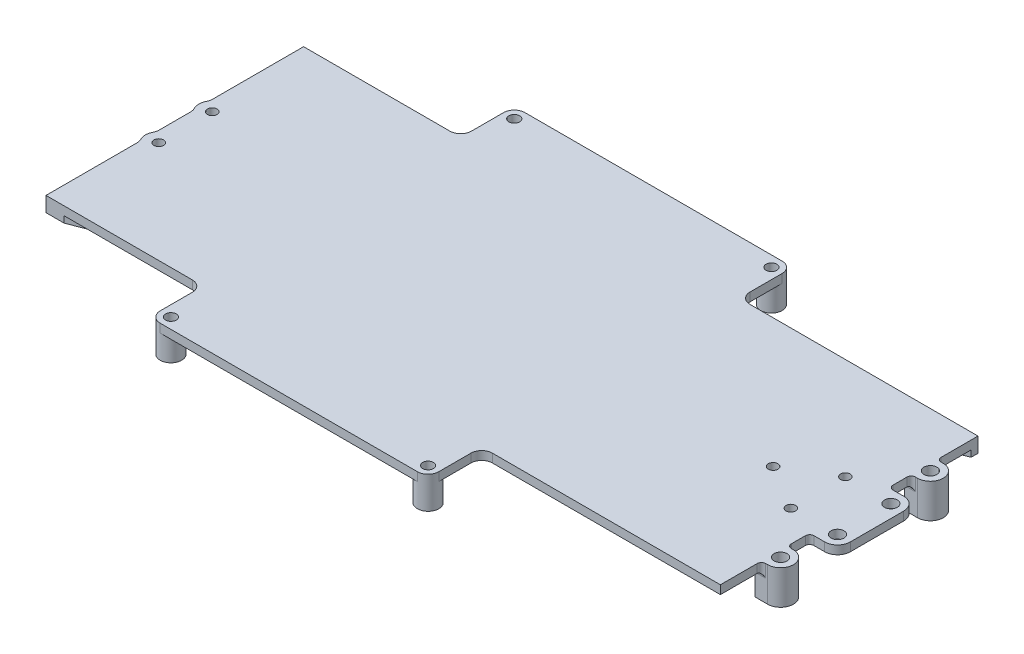
SolidWorks part; units mm, degrees
ref_plane "Front Plane" through (0, 0, 0) normal (0, 0, 1) x (1, 0, 0)
ref_plane "Top Plane" through (0, 0, 0) normal (0, 1, 0) x (1, 0, 0)
ref_plane "Right Plane" through (0, 0, 0) normal (1, 0, 0) x (0, 0, -1)
ref_point "Point1"
ref_point "Point2"
sketch "Sketch1" plane through (0, 0, 0) normal (0, 1, 0) x (1, 0, 0)
  line L0 (-51.1882, 59.7128) -> (-51.1882, -20.4872)
  line L1 (-51.1882, 59.7128) -> (-51.1882, 79.7128)
  line L2 (-51.1882, -20.4872) -> (-51.1882, -40.4872)
  line L3 (-51.1882, 19.6128) -> (263.4918, 19.6128)
  line L4 (-51.1882, 79.7128) -> (263.4918, 79.7128)
  line L5 (263.4918, 79.7128) -> (263.4918, -40.4872)
  line L6 (263.4918, -40.4872) -> (-51.1882, -40.4872)
  line L7 (-51.1882, 79.7128) -> (263.4918, -40.4872)
  line L8 (-51.1882, -40.4872) -> (263.4918, 79.7128)
  line L9 (-42.7808, -40.4872) -> (263.4918, 76.5014)
  line L10 (-51.1882, 76.5014) -> (255.0845, -40.4872)
  line L11 (-51.1882, -37.2758) -> (255.0845, 79.7128)
  line L12 (-42.7808, 79.7128) -> (263.4918, -37.2758)
  line L13 (-50.1177, 82.5153) -> (264.5623, -37.6847) construction
  line L14 (-52.2586, 76.9103) -> (262.4214, -43.2897) construction
  line L15 (-52.2586, -37.6847) -> (262.4214, 82.5153) construction
  line L16 (-50.1177, -43.2897) -> (264.5623, 76.9103) construction
  line L17 (-58.1882, 32.0578) -> (-58.1882, 7.1678)
  line L18 (-51.1882, 19.6128) -> (-58.1882, 19.6128)
  line L19 (-64.1882, 32.0578) -> (-64.1882, 7.1678)
  line L20 (106.1518, -40.4872) -> (106.1518, -15.2697)
  line L21 (-58.1882, 1.1678) -> (-51.1882, 1.1678)
  line L22 (-58.1882, 38.0578) -> (-51.1882, 38.0578)
  line L23 (270.4918, 1.1678) -> (263.4918, 1.1678)
  line L24 (276.4918, 32.0578) -> (276.4918, 7.1678)
  line L25 (270.4918, 38.0578) -> (263.4918, 38.0578)
  line L26 (-51.1882, 59.7128) -> (269.4218, 59.7128)
  line L27 (-51.1882, -20.4872) -> (269.4218, -20.4872)
  circle A0 centre (-58.1882, 32.0578) radius 3
  circle A1 centre (-58.1882, 7.1678) radius 3
  circle A3 centre (-58.1882, 32.0578) radius 6
  circle A4 centre (-58.1882, 7.1678) radius 6
  circle A5 centre (270.4918, 7.1678) radius 3
  circle A6 centre (270.4918, 7.1678) radius 6
  circle A7 centre (270.4918, 32.0578) radius 3
  circle A8 centre (270.4918, 32.0578) radius 6
  point P28 (-58.1882, 19.6128)
  dimension "D8" = 6
  dimension "D9" = 6
  dimension "D1" = 20
  dimension "D2" = 20
  dimension "D3" = 314.68
  dimension "D6" = 24.89
  dimension "D7" = 7
  dimension "D4" = 3
  dimension "D5" = 3
  dimension "D10" = 3
extrude "Boss-Extrude1" add sketch "Sketch1" along normal blind 4 from offset 3 contours L5 | L5 | L24 A8 L25 L5 L23 A6 | A6 A5 | A8 A7 | L27 L12 L5 | L12 L27 L5 L3 | L26 L9 L3 L5 | L9 L26 L5 | L27 L20 L6 L10 | L9 L27 L10 | L27 L10 L6 L7 | L27 L7 L5 L12 | L7 L27 L12 L9 | L10 L27 L7 L9 | L8 L26 L9 L5 | L11 L26 L8 L4 | L26 L8 L12 L9 | L26 L11 L12 L8 | L12 L26 L11 L4 | L26 L12 L11 | L27 L9 L6 L20 | L12 L8 L3 | L7 L9 L3 | L8 L10 L9 L7 | L12 L11 L7 L8 | L3 L10 L8 | L11 L3 L7 | L8 L27 L9 L10 | L11 L27 L8 L10 | L0 L27 L11 L3 | L26 L7 L11 L12 | L26 L10 L11 L7 | L26 L0 L3 L10 | L27 L8 L6 L9 | L27 L11 L2 L8 | L27 L2 L11 | L7 L26 L12 L4 | L10 L26 L7 L1 | L1 L26 L10 region at (1.7945, 0, -36.0253) region at (-36.5375, 0, -65.309) region at (-27.0491, 0, -68.9333) region at (48.3855, 0, -40.0615) region at (1.7945, 0, -3.2003) region at (-20.8048, 0, -69.7128) region at (101.9482, 0, -20.148) region at (101.9482, 0, -19.0775) region at (48.3855, 0, 0.8359) region at (54.6901, 0, -40.8642) region at (106.1518, 0, -70.4237) region at (110.3555, 0, -20.148) region at (110.3555, 0, -19.0775) region at (106.1518, 0, -18.0071) region at (106.1518, 0, -21.2185) region at (54.6901, 0, 1.6386) region at (-27.0491, 0, 29.7077) region at (-36.5375, 0, 26.0834) region at (106.1518, 0, -47.4166) region at (233.1085, 0, -69.7128) region at (210.5092, 0, -36.0253) region at (163.9182, 0, 0.8359) region at (163.9182, 0, -40.0615) region at (210.5092, 0, -3.2003) region at (157.6136, 0, 1.6386) region at (157.6136, 0, -40.8642) region at (-20.8048, 0, 30.4872) region at (106.1518, 0, 8.191) region at (239.3528, 0, -68.9333) region at (269.1814, 0, -19.6128) region at (248.8412, 0, -65.309) region at (248.8412, 0, 26.0834) region at (239.3528, 0, 29.7077) region at (233.1085, 0, 30.4872) region at (43.8448, 0, 31.1981) region at (168.4589, 0, 31.1981) region at (274.6145, 0, -36.1804) region at (266.3692, 0, -11.2904)
sketch "Sketch2" plane through (-51.1882, 0, 0) normal (1, 0, 0) x (0, 0, -1)
  line L0 (-20.4872, -0.3116) -> (59.7128, -0.3116)
  line L1 (19.6128, -0.3116) -> (19.6128, -9.1391)
  line L2 (-20.4872, -0.3116) -> (-24.4872, -0.3116)
  line L3 (-13.9565, 3) -> (-17.0231, -2.3116)
  line L4 (-27.018, 3) -> (-13.9565, 3)
  line L5 (1.1678, 3) -> (-40.4872, 3) construction
  line L6 (-20.4872, -0.3116) -> (-20.4872, 3)
  line L7 (-27.018, 3) -> (-23.9513, -2.3116)
  line L8 (53.182, 3) -> (56.2487, -2.3116)
  line L9 (66.2435, 3) -> (53.182, 3)
  line L10 (66.2435, 3) -> (63.1769, -2.3116)
  circle A0 centre (-20.4872, -0.3116) radius 1
  circle A2 centre (-20.4872, -0.3116) radius 4
  circle A4 centre (59.7128, -0.3116) radius 1
  circle A5 centre (59.7128, -0.3116) radius 4
  line M19 (79.7128, 3) -> (-40.4872, 3)
  dimension "D1" = 3
  dimension "D2" = 2
  dimension "D4" = 60
extrude "Boss-Extrude2" add sketch "Sketch2" along normal blind 4 contours A5 L9 A4 | A5 L10 M19 | A5 L0 L8 M19 | A5 L8 L0 | L0 A2 L3 M19 | L3 A2 L0 | A2 L0 A0 L6 L4 | A2 L4 L6 A0 L2 | A2 L7 M19 | A2 L2 A0 L0 region at (-51.1882, 1.2944, 18.6137) region at (-51.1882, -2.0941, 20.4872) region at (-51.1882, 1.2944, 22.3607) region at (-51.1882, 1.8121, 15.9474) region at (-51.1882, -0.8257, 16.353) region at (-51.1882, 1.6583, 25.0034) region at (-51.1882, 1.8121, -55.173) region at (-51.1882, -0.8257, -55.5785) region at (-51.1882, 1.5119, -56.2748) region at (-51.1882, 1.6583, -64.229)
extrude "Boss-Extrude4" add sketch "Sketch1<3>" along normal blind 4 contours L10 L26 L7 L1 | L7 L26 L12 L4 | L26 L10 L11 L7 | L26 L7 L11 L12 | L27 L8 L6 L9 | L27 L11 L2 L8 | L8 L27 L9 L10 | L11 L27 L8 L10 | L10 L27 L7 L9 | L7 L27 L12 L9 | L7 L9 L3 | L12 L8 L3 | L8 L10 L9 L7 | L3 L10 L8 | L11 L3 L7 | L12 L11 L7 L8 | L26 L11 L12 L8 | L26 L8 L12 L9 | L8 L26 L9 L5 | L11 L26 L8 L4 | L27 L7 L5 L12 | L27 L10 L6 L7 region at (-27.0491, 0, -68.9333) region at (48.3855, 0, -40.0615) region at (-20.8048, 0, -69.7128) region at (101.9482, 0, -20.148) region at (101.9482, 0, -19.0775) region at (48.3855, 0, 0.8359) region at (54.6901, 0, -40.8642) region at (110.3555, 0, -20.148) region at (110.3555, 0, -19.0775) region at (106.1518, 0, -18.0071) region at (106.1518, 0, -21.2185) region at (54.6901, 0, 1.6386) region at (-27.0491, 0, 29.7077) region at (233.1085, 0, -69.7128) region at (163.9182, 0, 0.8359) region at (163.9182, 0, -40.0615) region at (157.6136, 0, 1.6386) region at (157.6136, 0, -40.8642) region at (-20.8048, 0, 30.4872) region at (239.3528, 0, -68.9333) region at (239.3528, 0, 29.7077) region at (233.1085, 0, 30.4872)
sketch "Sketch1<3>" plane through (0, 0, 0) normal (0, 1, 0) x (1, 0, 0) same geometry as "Sketch1"
chamfer "Chamfer1" distance 3 angle 45 2 edges at (259.2882, 0, 40.4872) (263.4918, 0, 38.8815) tangent propagation no
sketch "Sketch4" plane through (0, 0, 0) normal (0, 1, 0) x (1, 0, 0)
  line L0 (-51.1882, 79.7128) -> (-51.1882, -40.4872) construction
  line L1 (276.4918, 32.0578) -> (276.4918, 7.1678) construction
  line L3 (266.4218, 60.5628) -> (260.4218, 60.5628)
  line L5 (266.4218, 48.5628) -> (260.4218, 48.5628)
  line L6 (260.4218, 60.5628) -> (260.4218, 48.5628)
  circle A0 centre (266.4218, 54.5628) radius 3
  circle A1 centre (266.4218, 54.5628) radius 6
  point P6 (276.4918, 19.6128)
  dimension "D1" = 6
  dimension "D2" = 317.61
  dimension "D3" = 34.95
  dimension "D4" = 3
extrude "Boss-Extrude5" add sketch "Sketch4" against normal blind 16 from surface contours A1 A0 | A1 L6 L5 | A1 L3 L6 region at (261.7621, 0, -59.2226) region at (270.5445, 0, -58.6854) region at (261.7621, 0, -49.903) starting at face at (204.8044, 7, -19.6128)
extrude "Cut-Extrude2" cut sketch "Sketch4<2>" along normal blind 25 contours A0
sketch "Sketch4<2>" plane through (0, 0, 0) normal (0, 1, 0) x (1, 0, 0) same geometry as "Sketch4"
ref_plane "Plane2" through (276.4918, 7, -19.6128) normal (0, 0, 1) x (1, 0, 0)
mirror "Mirror2" about plane through (276.4918, 7, -19.6128) normal (0, 0, 1) of "Boss-Extrude5", "Cut-Extrude2"
fillet "Fillet1" radius 2 6 edges at (263.4918, 5, -1.1678) (263.4918, 5, -38.0578) (263.4918, 5, -48.5628) (263.4918, 5, -60.5628) (263.4918, 5, 9.3372) (263.4918, 5, 21.3372)
fillet "Fillet2" radius 2 6 edges at (262.9568, 3, -48.5628) (260.4218, 3, -54.5628) (262.9568, 3, -60.5628) (262.9568, 3, 9.3372) (260.4218, 3, 15.3372) (262.9568, 3, 21.3372)
sketch "Sketch5" plane through (0, 0, 0) normal (0, 1, 0) x (1, 0, 0)
  line L0 (-51.1882, 79.7128) -> (263.4918, 79.7128) construction
  line L1 (22.1018, 79.7128) -> (152.1018, 79.7128)
  line L2 (22.1018, 79.7128) -> (22.1018, 104.7128)
  line L3 (22.1018, 104.7128) -> (152.1018, 104.7128)
  line L4 (152.1018, 79.7128) -> (152.1018, 104.7128)
  line L5 (-51.1882, 79.7128) -> (-51.1882, -40.4872) construction
  line L6 (-51.1882, 19.6128) -> (17.7147, 19.6128)
  line L8 (152.1018, -40.4872) -> (152.1018, -65.4872)
  line L9 (22.1018, -65.4872) -> (152.1018, -65.4872)
  line L10 (22.1018, -40.4872) -> (22.1018, -65.4872)
  line L11 (22.1018, -40.4872) -> (152.1018, -40.4872)
  line L12 (-51.1882, 79.7128) -> (-51.1882, -40.4872) construction
  point P16 (87.1018, 104.7128)
  dimension "D1" = 130
  dimension "D3" = 25
  dimension "D4" = 138.29
extrude "Boss-Extrude6" add sketch "Sketch5" along normal up to surface (7 mm away) from surface contours L1 L4 L3 L2 | L11 L10 L9 L8 region at (87.1018, 0, -92.2128) region at (87.1018, 0, 52.9872) up to face at (266.4218, 7, 18.3372) starting at face at (106.1518, 3, 21.5244)
sketch "Sketch7" plane through (0, 7, 0) normal (0, 1, 0) x (1, 0, 0)
  line L0 (-51.1882, 19.6128) -> (-46.1882, 19.6128)
  line L1 (-51.1882, 79.7128) -> (-51.1882, -40.4872) construction
  line L2 (-46.1882, 19.6128) -> (-46.1882, 32.1128)
  line L3 (276.4918, 19.6128) -> (248.9918, 19.6128)
  line L4 (276.4918, 32.0578) -> (276.4918, 7.1678) construction
  line L5 (248.9918, 19.6128) -> (248.9918, 32.3228)
  circle A0 centre (-46.1882, 32.1128) radius 2.25
  circle A1 centre (-46.1882, 7.1128) radius 2.25
  circle A2 centre (-46.1882, 32.1128) radius 6.25
  circle A3 centre (-46.1882, 7.1128) radius 6.25
  circle A4 centre (248.9918, 32.3228) radius 2.25
  circle A5 centre (248.9918, 6.9028) radius 2.25
  circle A6 centre (227.9818, 19.6128) radius 2.25
  line M42 (-51.1882, 79.7128) -> (-51.1882, -40.4872)
  dimension "D3" = 4.5
  dimension "D7" = 4.5
  dimension "D8" = 4.5
  dimension "D1" = 5
  dimension "D2" = 12.5
  dimension "D5" = 27.5
  dimension "D6" = 12.71
  dimension "D9" = 21.01
  dimension "D4" = 4
extrude "Boss-Extrude8" add sketch "Sketch7" along normal up to surface from surface contours A2 M42 | A3 M42 region at (-51.6927, 7, -7.1128) region at (-51.6927, 7, -32.1128) up to face at (266.4218, 7, 18.3372) starting at face at (95.2661, 3, 39.5031)
fillet "Fillet3" radius 5 12 edges at (22.1018, 5, 65.4872) (22.1018, 5, 40.4872) (152.1018, 5, 65.4872) (152.1018, 5, 40.4872) (152.1018, 5, -79.7128) (152.1018, 5, -104.7128) (22.1018, 5, -104.7128) (22.1018, 5, -79.7128) (-51.1882, 5, -3.3628) (-51.1882, 5, -10.8628) (-51.1882, 5, -28.3628) (-51.1882, 5, -35.8628)
sketch "Sketch6" plane through (0, 0, 0) normal (0, 1, 0) x (1, 0, 0)
  line L0 (-51.1882, 26.9589) -> (-51.1882, 12.2667) construction
  line L2 (87.1018, -65.4872) -> (87.1018, -37.4823)
  line L3 (147.1018, -65.4872) -> (27.1018, -65.4872) construction
  line L4 (-51.1882, 19.6128) -> (-19.1176, 19.6128)
  circle A2 centre (27.1018, -60.4872) radius 5
  arc A3 (22.1018, -60.4872) -> (27.1018, -65.4872) centre (27.1018, -60.4872) ccw construction
  circle A4 centre (27.1018, -60.4872) radius 2.75
  circle A5 centre (147.1018, -60.4872) radius 2.75
  circle A6 centre (147.1018, -60.4872) radius 5
  circle A7 centre (147.1018, 99.7128) radius 5
  circle A8 centre (147.1018, 99.7128) radius 2.75
  circle A9 centre (27.1018, 99.7128) radius 2.75
  circle A10 centre (27.1018, 99.7128) radius 5
  circle A11 centre (27.1018, -60.4872) radius 2.5
  circle A12 centre (147.1018, -60.4872) radius 2.5
  circle A13 centre (147.1018, 99.7128) radius 2.5
  circle A14 centre (27.1018, 99.7128) radius 2.5
  point P23 (-35.1529, 19.6128)
  dimension "D1" = 5
  dimension "D3" = 5.5
extrude "Boss-Extrude7" add sketch "Sketch6" against normal blind 10 from surface contours A2 A4 | A6 A5 | A10 A9 | A7 A8 | A8 | A9 | A4 | A5 region at (22.2433, 0, 60.4872) region at (24.4296, 0, 60.4872) region at (144.4296, 0, 60.4872) region at (142.2433, 0, 60.4872) region at (142.2433, 0, -99.7128) region at (144.4296, 0, -99.7128) region at (24.4296, 0, -99.7128) region at (22.2433, 0, -99.7128) starting at face at (92.2973, 3, 44.4064)
extrude "Boss-Extrude9" add sketch "Sketch6<5>" against normal blind 1 from surface contours A6 | A2 | A7 | A10 starting at face at (27.1018, -7, 62.9872)
sketch "Sketch6<5>" plane through (0, 0, 0) normal (0, 1, 0) x (1, 0, 0) same geometry as "Sketch6"
extrude "Cut-Extrude4" cut sketch "Sketch7<4>" against normal blind 10 contours A0 | A1 region at (-47.7341, 7, -33.6588) region at (-46.1882, 7, -7.1128)
sketch "Sketch7<4>" plane through (0, 7, 0) normal (0, 1, 0) x (1, 0, 0) same geometry as "Sketch7"
sketch "Sketch3" plane through (0, 0, 0) normal (0, 1, 0) x (1, 0, 0)
  line L0 (-51.1882, 37.2667) -> (-51.1882, 79.7128) construction
  line L1 (-7.1882, 90.3323) -> (13.8118, 90.3323)
  line L2 (-7.1882, 90.3323) -> (-7.1882, 76.2128)
  line L3 (-7.1882, 76.2128) -> (13.8118, 76.2128)
  line L4 (13.8118, 90.3323) -> (13.8118, 76.2128)
  line L5 (-51.1882, 79.7128) -> (17.1018, 79.7128) construction
  dimension "D1" = 44
  dimension "D2" = 3.5
  dimension "D3" = 21
extrude "Cut-Extrude5" cut sketch "Sketch6<3>" along normal blind 3 from surface contours A5 | A8 | A9 | A4 region at (24.4296, 0, 60.4872) region at (144.4296, 0, 60.4872) region at (144.4296, 0, -99.7128) region at (24.4296, 0, -99.7128) starting at face at (27.1018, -7, -97.2128)
sketch "Sketch6<3>" plane through (0, 0, 0) normal (0, 1, 0) x (1, 0, 0) same geometry as "Sketch6"
extrude "Cut-Extrude8" cut sketch "Sketch6<4>" against normal blind 4 from surface contours A11 | A12 | A13 | A14 region at (27.1018, 0, 60.4872) region at (147.1018, 0, 60.4872) region at (147.1018, 0, -99.7128) region at (27.1018, 0, -99.7128) starting at face at (-46.1882, 7, -4.8628)
sketch "Sketch6<4>" plane through (0, 0, 0) normal (0, 1, 0) x (1, 0, 0) same geometry as "Sketch6"
extrude "Cut-Extrude9" cut sketch "Sketch7<5>" against normal blind 10 contours A4 | A5 | A6 region at (250.5378, 7, -30.7768) region at (248.9918, 7, -6.9028) region at (227.9818, 7, -19.6128)
sketch "Sketch7<5>" plane through (0, 7, 0) normal (0, 1, 0) x (1, 0, 0) same geometry as "Sketch7"
